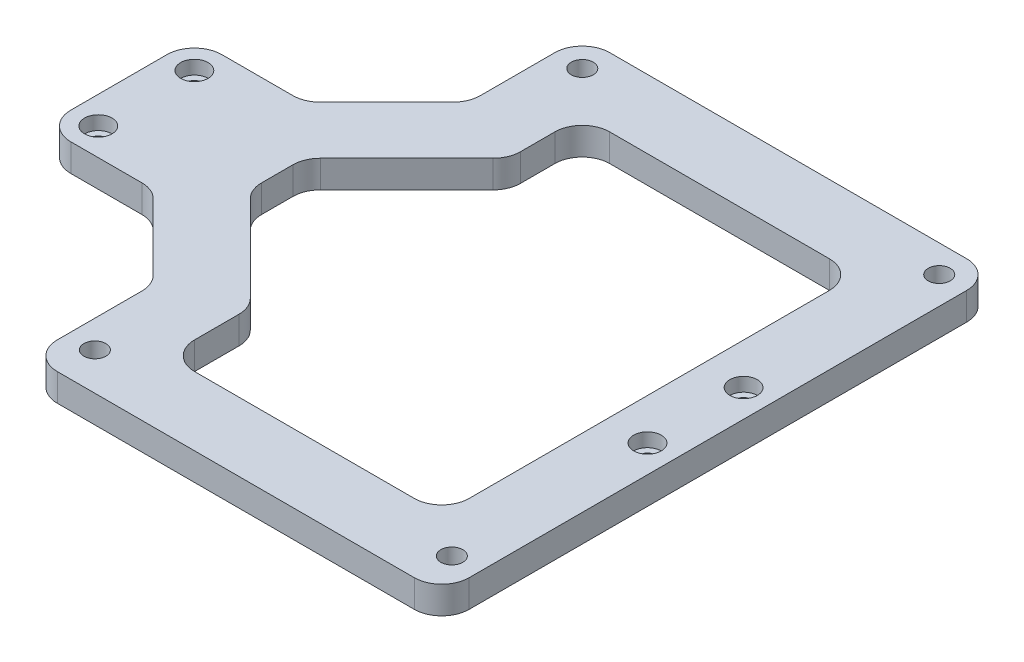
SolidWorks part; units mm, degrees
ref_plane "前视基准面" through (0, 0, 0) normal (0, 0, 1) x (1, 0, 0)
ref_plane "上视基准面" through (0, 0, 0) normal (0, 1, 0) x (1, 0, 0)
ref_plane "右视基准面" through (0, 0, 0) normal (1, 0, 0) x (0, 0, -1)
sketch "草图1" plane through (0, 0, 0) normal (0, 1, 0) x (1, 0, 0)
  line L0 (-47, 10) -> (-47, -10) construction
  line L1 (54.75, -31.5) -> (-54.75, -31.5) construction
  line L2 (54.75, -31.5) -> (54.75, 31.5) construction
  line L3 (54.75, 31.5) -> (-54.75, 31.5) construction
  line L4 (-54.75, -31.5) -> (-54.75, 31.5) construction
  line L5 (54.75, -31.5) -> (-54.75, 31.5) construction
  line L6 (54.75, 31.5) -> (-54.75, -31.5) construction
  line L7 (-29.75, 7) -> (-29.75, -7) construction
  line L8 (50.25, 7) -> (50.25, -7) construction
  line L9 (50.25, 0) -> (-29.75, 0) construction
  line L10 (-29.75, 0) -> (-47, 0) construction
  line L11 (-29.75, 7) -> (50.25, 7) construction
  circle A0 centre (-47, 10) radius 1.05
  circle A1 centre (-47, -10) radius 1.05
  circle A2 centre (-29.75, 7) radius 1.05
  circle A3 centre (-29.75, -7) radius 1.05
  circle A4 centre (50.25, 7) radius 1.05
  circle A5 centre (50.25, -7) radius 1.05
  point P0 (0, 0)
  dimension "D8" = 2.1
  dimension "D1" = 63
  dimension "D2" = 109.5
  dimension "D3" = 14
  dimension "D4" = 20
  dimension "D5" = 4.5
  dimension "D6" = 80
  dimension "D7" = 17.25
sketch "草图2" plane through (0, 0, 0) normal (0, 1, 0) x (1, 0, 0)
  line L0 (50.25, 0) -> (-29.75, 0) construction
  line L1 (54.25, -11) -> (-33.75, -11)
  line L2 (54.25, -11) -> (54.25, 11)
  line L3 (54.25, 11) -> (-33.75, 11)
  line L4 (-33.75, -11) -> (-33.75, 11)
  line L5 (54.25, -11) -> (-33.75, 11) construction
  line L6 (54.25, 11) -> (-33.75, -11) construction
  line L7 (50.25, 7) -> (50.25, -7) construction
  line L8 (-29.75, 7) -> (50.25, 7) construction
  line L9 (24.25, 25.25) -> (24.25, -25.9854) construction
  line L10 (54.25, -40.9708) -> (-5.75, -40.9708)
  line L11 (54.25, -40.9708) -> (54.25, -11)
  line L12 (54.25, -11) -> (-5.75, -11)
  line L13 (-5.75, -40.9708) -> (-5.75, -11)
  line L14 (54.25, -40.9708) -> (-5.75, -11) construction
  line L15 (54.25, -11) -> (-5.75, -40.9708) construction
  line L16 (54.25, 39.5) -> (-5.75, 39.5)
  line L17 (54.25, 39.5) -> (54.25, 11)
  line L18 (54.25, 11) -> (-5.75, 11)
  line L19 (-5.75, 39.5) -> (-5.75, 11)
  line L20 (54.25, 39.5) -> (-5.75, 11) construction
  line L21 (54.25, 11) -> (-5.75, 39.5) construction
  line L22 (-5.75, 11) -> (-5.75, -11) construction
  line L23 (54.75, 31.5) -> (-54.75, 31.5) construction
  line L24 (-1.75, 35.5) -> (50.25, 35.5) construction
  line L25 (50.25, 35.5) -> (50.25, -35.5) construction
  line L26 (50.25, -35.5) -> (-1.75, -35.5) construction
  line L27 (-1.75, -35.5) -> (-1.75, 35.5) construction
  line L28 (24.25, 35.5) -> (24.25, 25.25) construction
  line L29 (50.25, 0) -> (10.25, 0) construction
  circle A0 centre (-1.75, 35.5) radius 1.6
  circle A1 centre (-29.75, 7) radius 1.05
  circle A2 centre (-29.75, -7) radius 1.05
  circle A3 centre (50.25, 7) radius 1.05
  circle A4 centre (50.25, -7) radius 1.05
  circle A5 centre (50.25, 35.5) radius 1.6
  circle A6 centre (50.25, -35.5) radius 1.6
  circle A7 centre (-1.75, -35.5) radius 1.6
  point P0 (10.25, 0)
  point P23 (24.25, -25.9854)
  point P28 (24.25, 25.25)
  point P36 (52.0433, 11)
  dimension "D1" = 2.1
  dimension "D6" = 3.2
  dimension "D2" = 4
  dimension "D3" = 4
  dimension "D4" = 8
  dimension "D5" = 60
  dimension "D7" = 4
  dimension "D8" = 4
extrude "凸台-拉伸1" add sketch "草图2" along normal blind 4 contours L4 L1 L2 L3 A4 A3 A2 A1 | L16 L19 L3 L17 | L13 L10 L11 L1 region at (24.25, 0, 25.8995) region at (10.25, 0, 0) region at (24.25, 0, -25.1527)
sketch "草图3" plane through (0, 4, 0) normal (0, 1, 0) x (1, 0, 0)
  circle A1 centre (-29.75, 7) radius 2
  circle A2 centre (-29.75, -7) radius 2
  circle A3 centre (50.25, 7) radius 2
  circle A4 centre (50.25, -7) radius 2
  dimension "D1" = 4
extrude "切除-拉伸1" cut sketch "草图3" against normal blind 2
chamfer "倒角1" distance 12 angle 45 2 edges at (-5.75, 2, 11) (-5.75, 2, -11)
sketch "草图5" plane through (0, 0, 0) normal (0, -1, 0) x (1, 0, 0)
  line L28 (-10.6789, 3.9289) -> (-10.6789, -3.9289)
  line L35 (4.25, 30.9708) -> (4.25, 18.8579)
  line L36 (4.25, 18.8579) -> (-10.6789, 3.9289)
  line L37 (-10.6789, -3.9289) -> (4.25, -18.8579)
  line L38 (4.25, -18.8579) -> (4.25, -29.5)
  line L39 (4.25, -29.5) -> (44.25, -29.5)
  line L40 (44.25, -29.5) -> (44.25, 30.9708)
  line L41 (44.25, 30.9708) -> (4.25, 30.9708)
  line L42 (4.25, 30.9708) -> (4.25, 18.8579)
  line L43 (4.25, 18.8579) -> (-10.6789, 3.9289)
  line L44 (-10.6789, -3.9289) -> (4.25, -18.8579)
  line L45 (4.25, -18.8579) -> (4.25, -29.5)
  line L46 (4.25, -29.5) -> (44.25, -29.5)
  line L47 (44.25, -29.5) -> (44.25, 30.9708)
  line L48 (44.25, 30.9708) -> (4.25, 30.9708)
  dimension "D1" = 10
extrude "切除-拉伸2" cut sketch "草图5" against normal up to next
fillet "圆角1" radius 4 10 edges at (-33.75, 2, -11) (54.25, 2, -39.5) (54.25, 2, 40.9708) (-5.75, 2, 40.9708) (-33.75, 2, 11) (-5.75, 2, -39.5) (-5.75, 2, 23) (-5.75, 2, -23) (-17.75, 2, -11) (-17.75, 2, 11)
fillet "圆角2" radius 4 8 edges at (44.25, 2, 30.9708) (44.25, 2, -29.5) (4.25, 2, -18.8579) (-10.6789, 2, -3.9289) (-10.6789, 2, 3.9289) (4.25, 2, 18.8579) (4.25, 2, 30.9708) (4.25, 2, -29.5)
